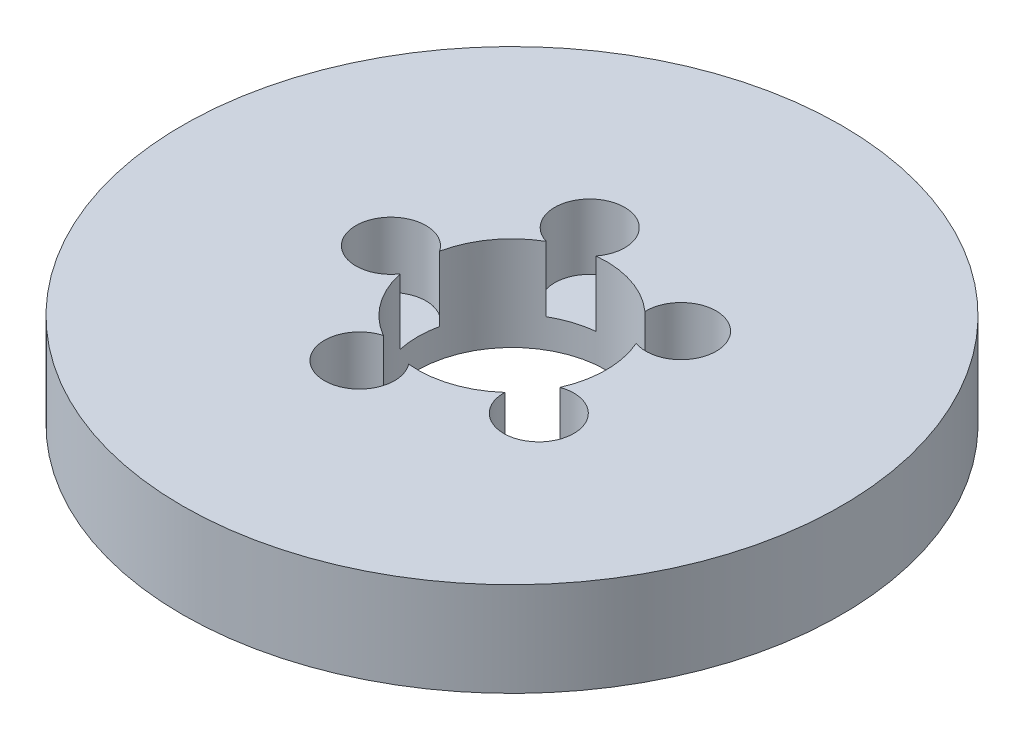
SolidWorks part; units mm, degrees
ref_plane "Front Plane" through (0, 0, 0) normal (0, 0, 1) x (1, 0, 0)
ref_plane "Top Plane" through (0, 0, 0) normal (0, 1, 0) x (1, 0, 0)
ref_plane "Right Plane" through (0, 0, 0) normal (1, 0, 0) x (0, 0, -1)
sketch "Sketch1" plane through (0, 0, 0) normal (0, 1, 0) x (1, 0, 0)
  circle A0 centre (0, 0) radius 35
  dimension "FLANGE_OD" = 70
extrude "Boss-Extrude1" add sketch "Sketch1" along normal blind 10
sketch "Sketch2" plane through (0, 0, 0) normal (0, 1, 0) x (1, 0, 0)
  circle A0 centre (0, 0) radius 10
  dimension "BORE_D" = 20
extrude "Cut-Extrude1" cut sketch "Sketch2" along normal through all
sketch "Sketch3" plane through (0, 10, 0) normal (0, 1, 0) x (1, 0, 0)
  circle A0 centre (0, 0) radius 12.8552 construction
  circle A1 centre (-12.8552, 0) radius 3.723
  dimension "BOLT_D" = 7.4461
  dimension "BOLT_PCD" = 25.7103
extrude "Cut-Extrude2" cut sketch "Sketch3" against normal blind 6.9329
pattern_circular "CirPattern1" count 5 over 360 about axis through (0, 0, 0) along (0, 1, 0) of "Cut-Extrude2"
